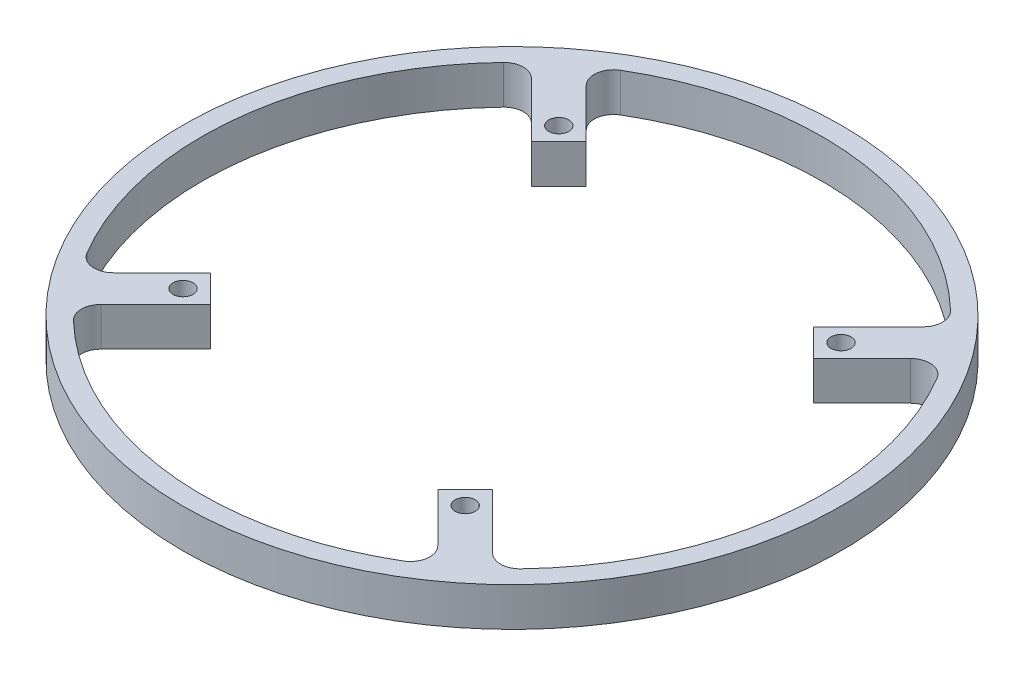
SolidWorks part; units mm, degrees
material "6061-T6 (SS)"
ref_plane "Front Plane" through (0, 0, 0) normal (0, 0, 1) x (1, 0, 0)
ref_plane "Top Plane" through (0, 0, 0) normal (0, 1, 0) x (1, 0, 0)
ref_plane "Right Plane" through (0, 0, 0) normal (1, 0, 0) x (0, 0, -1)
sketch "Sketch2" plane through (0, 0, 0) normal (1, 0, 0) x (0, 0, -1)
  line L0 (-55, 0) -> (-84.9998, 0)
  line L1 (-84.9998, 0) -> (-84.9998, 10)
  line L2 (-84.9998, 10) -> (-55, 10)
  line L5 (-55, 10) -> (-55, 0)
  dimension "D1" = 84.9998
  dimension "D2" = 10
  dimension "D3" = 55
ref_axis "Axis1" through (0, 3.6789, 0) along (0, 1, 0)
revolve "Revolve1" add sketch "Sketch2" angle 360 about axis through (0, 3.6789, 0) along (0, 1, 0)
sketch "Sketch9" plane through (0, 0, 0) normal (0, 1, 0) x (1, 0, 0)
  line L1 (42.4264, -42.4264) -> (-42.4264, -42.4264) construction
  line L2 (42.4264, -42.4264) -> (42.4264, 42.4264) construction
  line L3 (42.4264, 42.4264) -> (-42.4264, 42.4264) construction
  line L4 (-42.4264, -42.4264) -> (-42.4264, 42.4264) construction
  line L5 (0, 0) -> (0, 27.9091) construction
  line L7 (0, 0) -> (26.5726, 0) construction
  line L11 (-43.4619, 48.4619) -> (-36.3909, 55.533) construction
  line L12 (-43.4619, 48.4619) -> (-36.3909, 41.3909) construction
  line L13 (-36.3909, 55.533) -> (-29.3198, 48.4619) construction
  line L16 (-36.3909, 41.3909) -> (-36.3909, 55.533) construction
  line L18 (-43.4619, 48.4619) -> (-29.3198, 48.4619) construction
  line L20 (-29.3198, 48.4619) -> (-36.3909, 41.3909) construction
  point P3 (-42.4264, 42.4264)
  point P355 (-36.3909, 48.4619)
  dimension "D1" = 1.0355
  dimension "D2" = 60
  dimension "D3" = 6.0355
  dimension "D4" = 6.1237
hole_wizard "#6 (0.204) Diameter Hole1" positions "Sketch12" profile "Sketch13" hole size "#6" standard "ANSI Inch" end condition through all
sketch "Sketch12" plane through (0, 0, 0) normal (0, -1, 0) x (-1, 0, 0)
  point P0 (36.3909, 48.4619)
sketch "Sketch13" plane through (-36.3909, 0, -48.4619) normal (1, 0, 0) x (0, 0, -1)
  line L0 (0, 0) -> (0, 10)
  line L1 (0, 10) -> (2.5908, 10)
  line L2 (2.5908, 10) -> (2.5908, 0)
  line L5 (2.5908, 0) -> (0, 0)
  line L11 (0, -6.35) -> (0, 107.95) construction
  dimension "Thru Hole Dia." = 5.1816
  dimension "Thru Hole Depth" = 10
sketch "Sketch14" plane through (0, 0, 0) normal (0, -1, 0) x (1, 0, 0)
  line L0 (0, 0) -> (-36.3909, -48.4619) construction
  line L1 (-33.0708, -38.0708) -> (-54.0132, -59.0132)
  line L2 (-65.3239, 46.1818) -> (-55.533, 36.3909)
  line L3 (0, 0) -> (-48.4619, 36.3909) construction
  line L4 (-43.4619, -48.4619) -> (-36.3909, -41.3909) construction
  line L5 (-55.533, 36.3909) -> (-48.4619, 29.3198)
  line L6 (-41.3909, 36.3909) -> (-48.4619, 29.3198) construction
  line L7 (-41.3909, 36.3909) -> (-48.4619, 43.4619) construction
  line L8 (-48.4619, 43.4619) -> (-55.533, 36.3909) construction
  line L9 (-48.4619, 29.3198) -> (-55.533, 36.3909) construction
  line L10 (-41.3909, 36.3909) -> (-55.533, 36.3909) construction
  line L11 (-48.4619, 43.4619) -> (-48.4619, 29.3198) construction
  line L12 (-48.4619, 29.3198) -> (-41.3909, 36.3909)
  line L13 (-43.4619, -48.4619) -> (-36.3909, -55.533) construction
  line L14 (0, 0) -> (26.5726, 0) construction
  line L15 (-41.3909, 36.3909) -> (-38.0708, 33.0708)
  arc A0 (-33.0708, -38.0708) -> (-38.0708, 33.0708) centre (0, 0) cw
  arc A1 (-65.3239, 46.1818) -> (-54.0132, -59.0132) centre (0, 0) ccw
  circle A2 centre (0, 0) radius 84.9998 construction
  point P14 (-48.4619, 36.3909)
  dimension "D2" = 5
  dimension "D3" = 50.4288
extrude "Cut-Extrude1" cut sketch "Sketch14" against normal through all
pattern_circular "CirPattern1" count 4 over 360 about axis through (0, 3.6789, 0) along (0, 1, 0) of "Cut-Extrude1", "#6 (0.204) Diameter Hole1"
fillet "Fillet1" radius 5 8 edges at (54.0132, 5, 59.0132) (-54.0132, 5, -59.0132) (59.0132, 5, -54.0132) (-59.0132, 5, 54.0132) (46.1818, 5, 65.3239) (65.3239, 5, -46.1818) (-46.1818, 5, -65.3239) (-65.3239, 5, 46.1818)
